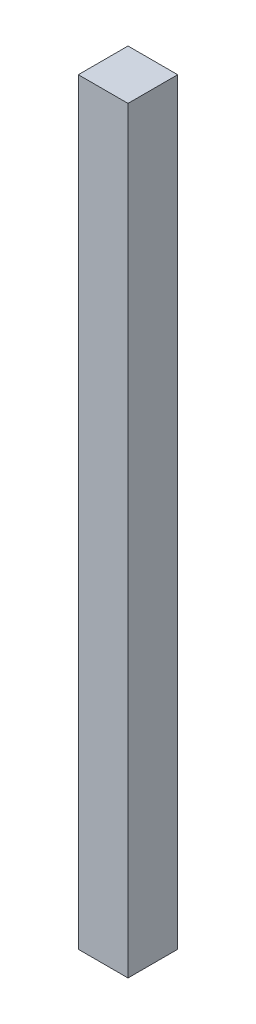
SolidWorks part; units mm, degrees
ref_plane "Front Plane" through (0, 0, 0) normal (0, 0, 1) x (1, 0, 0)
ref_plane "Top Plane" through (0, 0, 0) normal (0, 1, 0) x (1, 0, 0)
ref_plane "Right Plane" through (0, 0, 0) normal (1, 0, 0) x (0, 0, -1)
sketch "Sketch1" plane through (0, 0, 0) normal (0, 1, 0) x (1, 0, 0)
  line L1 (0, 0) -> (25.4, 0)
  line L2 (0, 0) -> (0, 25.4)
  line L3 (0, 25.4) -> (25.4, 25.4)
  line L4 (25.4, 0) -> (25.4, 25.4)
  dimension "D1" = 25.4
  dimension "D2" = 25.4
extrude "Boss-Extrude1" add sketch "Sketch1" along normal blind 387.096
